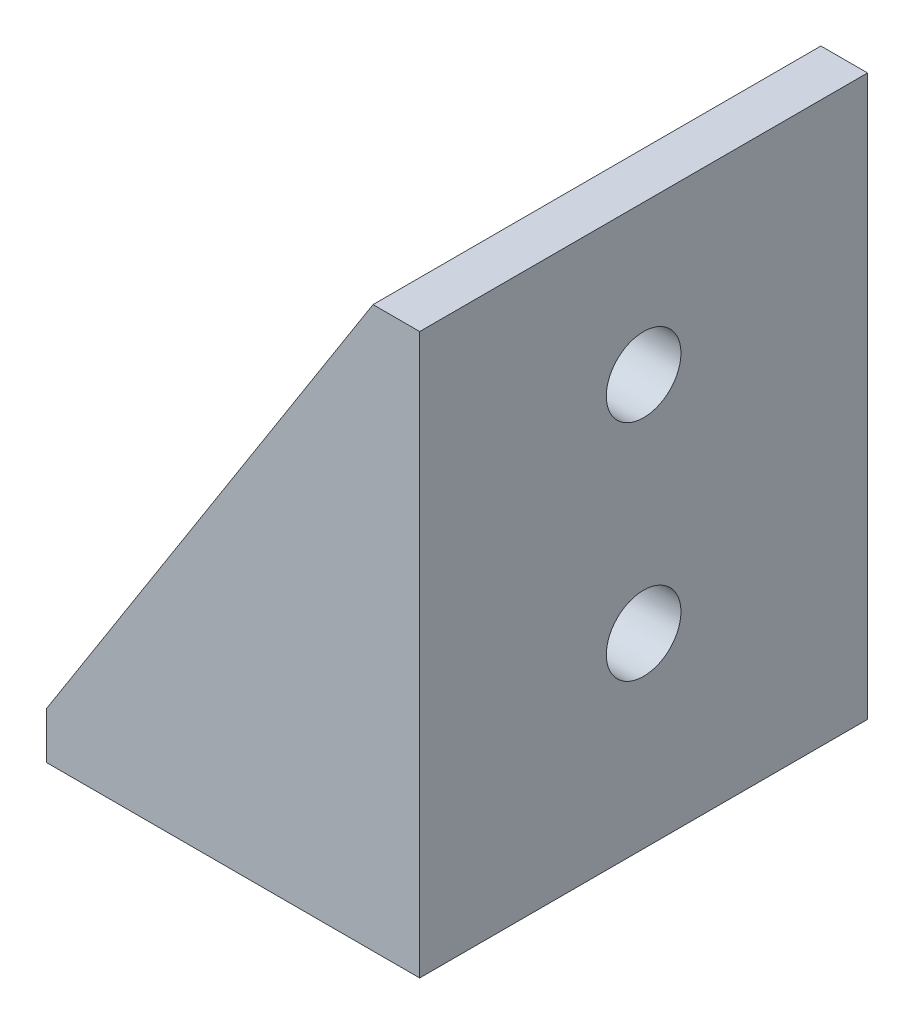
SolidWorks part; units mm, degrees
material "聚脂树脂"
ref_plane "前视基准面" through (0, 0, 0) normal (0, 0, 1) x (1, 0, 0)
ref_plane "上视基准面" through (0, 0, 0) normal (0, 1, 0) x (1, 0, 0)
ref_plane "右视基准面" through (0, 0, 0) normal (1, 0, 0) x (0, 0, -1)
other "Configuration Table"
sketch "草图1" plane through (0, 0, 0) normal (0, 0, 1) x (1, 0, 0)
  line L0 (0, 0) -> (20, 0)
  line L1 (20, 0) -> (20, 30)
  line L2 (20, 30) -> (17.5, 30)
  line L3 (17.5, 30) -> (0, 2.5)
  line L4 (0, 2.5) -> (0, 0)
  dimension "D1" = 30
  dimension "D2" = 2.5
  dimension "D3" = 20
extrude "凸台-拉伸1" add sketch "草图1" against normal blind 20
sketch "草图2" plane through (0, 0, 0) normal (0, 1, 0) x (1, 0, 0)
  line L0 (17.5, 20) -> (17.5, 0) construction
  line L1 (17.5, 18.3) -> (0, 18.3)
  line L2 (17.5, 18.3) -> (17.5, 1.7)
  line L3 (17.5, 1.7) -> (0, 1.7)
  line L4 (0, 18.3) -> (0, 1.7)
  line L5 (0, 20) -> (0, 0) construction
  line L6 (17.5, 20) -> (0, 20) construction
  line L7 (17.5, 0) -> (0, 0) construction
  dimension "D1" = 1.7
  dimension "D2" = 1.7
extrude "切除-拉伸1" cut sketch "草图2" against normal blind 27.5 from surface starting at face at (18.75, 30, -10)
sketch "草图3" plane through (0, 0, 0) normal (1, 0, 0) x (0, 0, -1)
  line L0 (10, -0.9294) -> (10, 20.6169) construction
  line L1 (20, 30) -> (0, 30) construction
  circle A0 centre (10, 22) radius 2
  circle A1 centre (10, 10) radius 2
  dimension "D1" = 4
  dimension "D2" = 10
  dimension "D3" = 12
  dimension "D4" = 8
extrude "切除-拉伸2" cut sketch "草图3" along normal up to next from surface starting at face at (17.5, 16.25, -10)
sketch "草图4" plane through (0, 0, 0) normal (0, 1, 0) x (1, 0, 0)
  line L0 (20, 20) -> (20, 0) construction
  circle A0 centre (9, 10) radius 1.7
  dimension "D3" = 3.4
  dimension "D1" = 10
  dimension "D2" = 11
sketch "草图5" plane through (17.5, 0, 0) normal (-1, 0, 0) x (0, 0, 1)
  line L4 (-1.7, 30) -> (-18.3, 30)
  line L5 (-18.3, 30) -> (-18.3, 2.5)
  line L6 (-18.3, 2.5) -> (-1.7, 2.5)
  line L7 (-1.7, 2.5) -> (-1.7, 30)
  line L8 (-1.7, 30) -> (-18.3, 30)
  line L9 (-18.3, 30) -> (-18.3, 2.5)
  line L10 (-18.3, 2.5) -> (-1.7, 2.5)
  line L11 (-1.7, 2.5) -> (-1.7, 30)
  dimension "D1" = 0
sketch "草图6" plane through (0, 0, -1.7) normal (0, 0, -1) x (-1, 0, 0)
  line L0 (-15.3, 26.5429) -> (-15.3, 2.5)
  line L3 (-17.5, 30) -> (-17.5, 2.5)
  line L4 (-17.5, 2.5) -> (0, 2.5)
  line L5 (0, 2.5) -> (-17.5, 30)
  line L6 (-17.5, 30) -> (-17.5, 2.5)
  line L7 (-17.5, 2.5) -> (-15.3, 2.5)
  line L8 (-15.3, 26.5429) -> (-17.5, 30)
  dimension "D2" = 2.2
  dimension "D1" = 0
extrude "凸台-拉伸3" add sketch "草图6" along normal up to next
extrude "切除-拉伸4" cut sketch "草图3<2>" against normal blind 2 and the other way through all
sketch "草图3<2>" plane through (0, 0, 0) normal (1, 0, 0) x (0, 0, -1) same geometry as "草图3"
extrude "切除-拉伸6" cut sketch "草图4" against normal blind 9 and the other way through all contours A0
sketch "草图7" plane through (0, 2.5, 0) normal (0, 1, 0) x (1, 0, 0)
  line L4 (15.3, 1.7) -> (15.3, 18.3)
  line L5 (15.3, 18.3) -> (0, 18.3)
  line L6 (0, 18.3) -> (0, 1.7)
  line L7 (0, 1.7) -> (15.3, 1.7)
  line L8 (15.3, 1.7) -> (15.3, 18.3)
  line L9 (15.3, 18.3) -> (0, 18.3)
  line L10 (0, 18.3) -> (0, 1.7)
  line L11 (0, 1.7) -> (15.3, 1.7)
  circle A0 centre (9, 10) radius 1.7 construction
  circle A1 centre (9, 10) radius 1.7
  dimension "D1" = 0
extrude "凸台-拉伸4" add sketch "草图7" along normal blind 2
sketch "草图8" plane through (0, 0, -20) normal (0, 0, -1) x (-1, 0, 0)
  line L5 (0, 0) -> (0, 2.5)
  line L6 (0, 2.5) -> (-17.5, 30)
  line L7 (-17.5, 30) -> (-20, 30)
  line L8 (-20, 30) -> (-20, 0)
  line L9 (-20, 0) -> (0, 0)
  line L10 (0, 0) -> (0, 2.5)
  line L11 (0, 2.5) -> (-17.5, 30)
  line L12 (-17.5, 30) -> (-20, 30)
  line L13 (-20, 30) -> (-20, 0)
  line L14 (-20, 0) -> (0, 0)
  dimension "D1" = 0
extrude "凸台-拉伸5" add sketch "草图8" along normal blind 2
extrude "凸台-拉伸6" add sketch "草图8<2>" against normal blind 2 from surface starting at face at (11.5, 12.5, 0)
sketch "草图8<2>" plane through (0, 0, -20) normal (0, 0, -1) x (-1, 0, 0) same geometry as "草图8"
